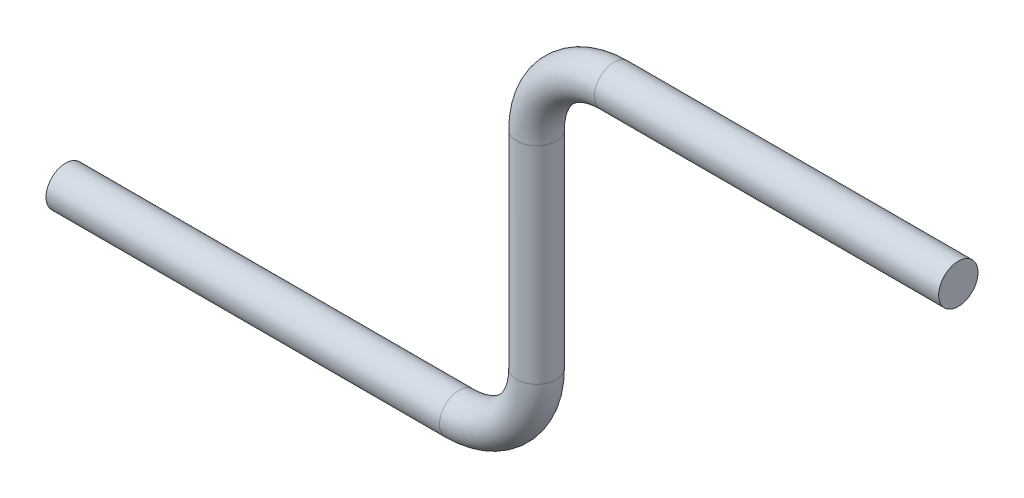
SolidWorks part; units mm, degrees
ref_plane "Front" through (0, 0, 0) normal (0, 0, 1) x (1, 0, 0)
ref_plane "Top" through (0, 0, 0) normal (0, 1, 0) x (1, 0, 0)
ref_plane "Right" through (0, 0, 0) normal (1, 0, 0) x (0, 0, -1)
sketch "Sketch1" plane through (0, 0, 0) normal (0, 0, 1) x (1, 0, 0)
  line L0 (-15.5632, 0) -> (24.4368, 0)
  line L1 (55, 0) -> (-55, 0) construction
  line L2 (32.3103, 7.8735) -> (32.3103, 28.8735)
  line L3 (40.1838, 36.747) -> (75.1838, 36.747)
  arc A0 (24.4368, 0) -> (32.3103, 7.8735) centre (24.4368, 7.8735) ccw
  arc A1 (40.1838, 36.747) -> (32.3103, 28.8735) centre (40.1838, 28.8735) ccw
  point P8 (24.4368, 0)
  point P12 (32.3103, 28.8735)
  dimension "D3" = 15.747
  dimension "D4" = 15.747
  dimension "D1" = 40
  dimension "D2" = 35
  dimension "D5" = 21
ref_plane "Plane1" through (-15.5632, 0, 0) normal (1, 0, 0) x (0, 0, -1)
sketch "Sketch3" plane through (-15.5632, 0, 0) normal (1, 0, 0) x (0, 0, -1)
  circle A0 centre (0, 0) radius 2
  point P0 (0, 0)
  dimension "D1" = 4
sweep "Sweep1" add profiles "Sketch3" path "Sketch1"
